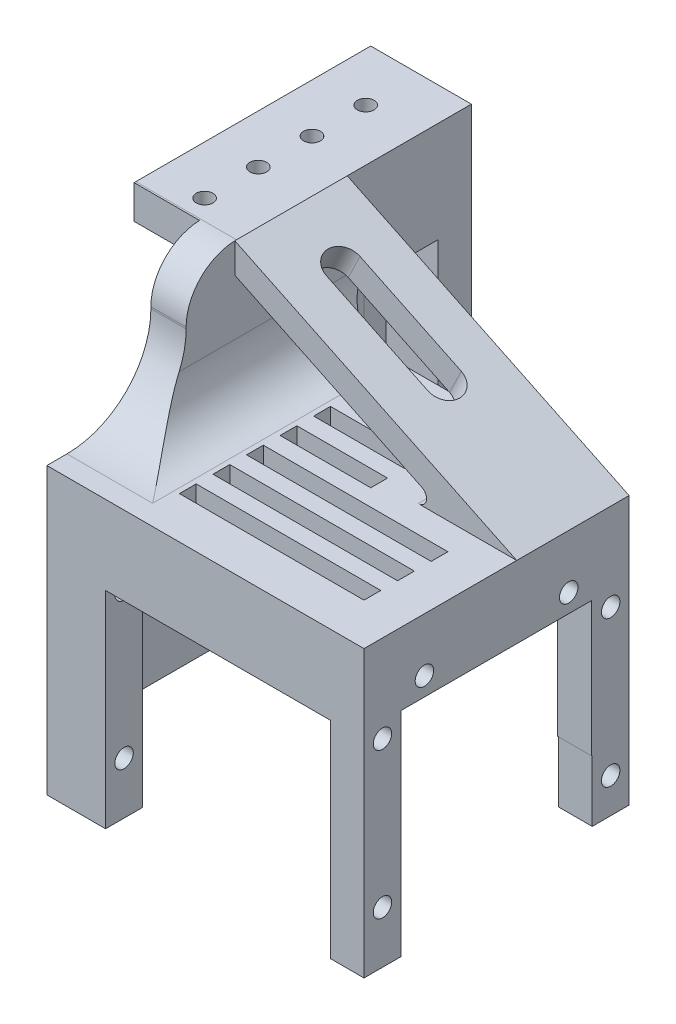
SolidWorks part; units mm, degrees
ref_plane "Front Plane" through (0, 0, 0) normal (0, 0, 1) x (1, 0, 0)
ref_plane "Top Plane" through (0, 0, 0) normal (0, 1, 0) x (1, 0, 0)
ref_plane "Right Plane" through (0, 0, 0) normal (1, 0, 0) x (0, 0, -1)
sketch "Sketch1" plane through (0, 0, 0) normal (0, 0, 1) x (1, 0, 0)
  line L1 (0, 0) -> (57.912, 0)
  line L2 (0, 0) -> (0, 63.754)
  line L3 (0, 63.754) -> (57.912, 63.754)
  line L4 (57.912, 0) -> (57.912, 63.754)
  dimension "D1" = 57.912
  dimension "D2" = 63.754
extrude "Boss-Extrude1" add sketch "Sketch1" against normal blind 58.928
sketch "Sketch3" plane through (0, 0, 0) normal (0, 0, 1) x (1, 0, 0)
  line L0 (42.672, 63.754) -> (0, 43.18)
  line L1 (42.672, 59.2423) -> (14.3644, 45.594)
  line L2 (14.9159, 43.18) -> (42.672, 43.18)
  line L3 (44.437, 60.0933) -> (1.765, 39.5193) construction
  line L4 (0, 63.754) -> (0, 0)
  line L5 (0, 0) -> (57.912, 0)
  line L6 (57.912, 0) -> (57.912, 63.754)
  line L7 (57.912, 63.754) -> (0, 63.754)
  line L8 (0, 63.754) -> (0, 43.18)
  line L9 (5.08, 0) -> (5.08, 31.242)
  line L10 (0, 0) -> (57.912, 0) construction
  line L11 (42.672, 63.754) -> (0, 63.754)
  line L12 (42.672, 59.2423) -> (42.672, 43.18)
  line L13 (5.08, 31.242) -> (39.116, 31.242)
  line L14 (39.116, 31.242) -> (39.116, 0)
  line L15 (5.08, 0) -> (39.116, 0)
  line L16 (48.006, 0) -> (48.006, 11.938)
  line L17 (48.006, 11.938) -> (57.912, 11.938)
  line L18 (57.912, 0) -> (57.912, 63.754) construction
  line L19 (57.912, 11.938) -> (57.912, 0)
  line L20 (48.006, 0) -> (57.912, 0)
  arc A0 (14.3644, 45.594) -> (14.9159, 43.18) centre (14.9159, 44.45) ccw
  dimension "D5" = 1.27
  dimension "D2" = 15.24
  dimension "D3" = 20.574
  dimension "D7" = 5.08
  dimension "D8" = 31.242
  dimension "D9" = 34.036
  dimension "D10" = 9.906
  dimension "D11" = 11.938
  dimension "D1" = 0
  dimension "D4" = 4.064
extrude "Cut-Extrude1" cut sketch "Sketch3" against normal through all
sketch "Sketch4" plane through (0, 63.754, 0) normal (0, 1, 0) x (1, 0, 0)
  line L0 (0, 0) -> (0, 18.796)
  line L1 (0, 58.928) -> (0, 0) construction
  line L2 (0, 18.796) -> (42.672, 18.796)
  line L3 (42.672, 58.928) -> (42.672, 0) construction
  line L4 (42.672, 18.796) -> (42.672, 0)
  line L5 (42.672, 0) -> (0, 0)
  line L6 (57.912, 35.814) -> (48.006, 35.814)
  line L7 (57.912, 58.928) -> (57.912, 0) construction
  line L8 (48.006, 35.814) -> (48.006, 58.928)
  line L9 (48.006, 58.928) -> (57.912, 58.928)
  line L10 (57.912, 58.928) -> (57.912, 35.814)
  line L11 (50.546, 35.814) -> (50.546, 32.512) construction
  circle A0 centre (50.546, 32.512) radius 1.27
  circle A1 centre (50.546, 24.384) radius 1.27
  circle A2 centre (50.546, 16.256) radius 1.27
  circle A3 centre (50.546, 8.128) radius 1.27
  dimension "D5" = 2.54
  dimension "D1" = 18.796
  dimension "D2" = 9.906
  dimension "D3" = 7.366
  dimension "D4" = 3.302
  dimension "D8" = 35.814
  dimension "D6" = 4
extrude "Cut-Extrude2" cut sketch "Sketch4" against normal through all
fillet "Fillet1" radius 2.54 1 edges at (42.672, 21.59, -18.796)
sketch "Sketch6" plane through (0, 63.754, 0) normal (0, 1, 0) x (1, 0, 0)
  line L0 (42.672, 35.814) -> (0, 35.814)
  line L1 (0, 58.928) -> (0, 18.796) construction
  line L2 (0, 35.814) -> (0, 58.928)
  line L3 (0, 58.928) -> (48.006, 58.928)
  line L4 (48.006, 58.928) -> (48.006, 43.18)
  line L5 (48.006, 58.928) -> (48.006, 35.814) construction
  line L6 (48.006, 43.18) -> (42.672, 43.18)
  line L7 (42.672, 58.928) -> (42.672, 18.796) construction
  line L8 (42.672, 43.18) -> (42.672, 35.814)
  line L9 (48.006, 35.814) -> (57.912, 35.814) construction
  dimension "D1" = 15.748
extrude "Cut-Extrude3" cut sketch "Sketch6" against normal blind 20.574
fillet "Fillet2" radius 12.7 1 edges at (45.339, 43.18, -43.18)
fillet "Fillet3" radius 7.62 1 edges at (42.672, 43.18, -36.068)
fillet "Fillet4" radius 7.62 1 edges at (45.339, 63.754, -43.18)
sketch "Sketch7" plane through (-16.8922, 35.0356, 0) normal (-0.4343, 0.9008, 0) x (0.9008, 0.4343, 0)
  line L0 (57.4899, 18.796) -> (57.4899, 24.638) construction
  line L1 (18.753, 18.796) -> (66.1259, 18.796) construction
  line L2 (57.4899, 24.638) -> (66.1259, 24.638) construction
  line L4 (57.4899, 24.638) -> (40.4719, 24.638)
  line L5 (57.4899, 29.718) -> (40.4719, 29.718)
  line L6 (66.1259, 35.56) -> (66.1259, 18.796) construction
  arc A0 (40.4719, 29.718) -> (40.4719, 24.638) centre (40.4719, 27.178) ccw
  arc A1 (57.4899, 29.718) -> (57.4899, 24.638) centre (57.4899, 27.178) cw
  dimension "D1" = 8.636
  dimension "D2" = 5.842
  dimension "D4" = 17.018
  dimension "D3" = 5.08
extrude "Cut-Extrude4" cut sketch "Sketch7" along direction (-0.4343, 0.9008, 0) on the side against the normal up to next (4.064 mm away)
sketch "Sketch8" plane through (0, 43.18, 0) normal (0, 1, 0) x (1, 0, 0)
  line L0 (6.35, 52.578) -> (34.29, 52.578)
  line L1 (34.29, 52.578) -> (34.29, 50.038)
  line L2 (34.29, 50.038) -> (6.35, 50.038)
  line L3 (6.35, 50.038) -> (6.35, 52.578)
  line L4 (0, 58.928) -> (0, 35.814) construction
  line L5 (0, 58.928) -> (48.006, 58.928) construction
  line L6 (34.29, 44.958) -> (6.35, 44.958)
  line L7 (34.29, 47.498) -> (34.29, 44.958)
  line L8 (6.35, 47.498) -> (34.29, 47.498)
  line L9 (6.35, 44.958) -> (6.35, 47.498)
  line L10 (34.29, 39.878) -> (6.35, 39.878)
  line L11 (34.29, 42.418) -> (34.29, 39.878)
  line L12 (6.35, 42.418) -> (34.29, 42.418)
  line L13 (6.35, 39.878) -> (6.35, 42.418)
  line L14 (34.29, 37.338) -> (20.574, 37.338)
  line L15 (34.29, 37.338) -> (34.29, 34.798)
  line L16 (34.29, 34.798) -> (20.574, 34.798)
  line L17 (20.574, 34.798) -> (20.574, 37.338)
  line L18 (34.29, 37.338) -> (6.35, 37.338) construction
  line L19 (34.29, 29.718) -> (20.574, 29.718)
  line L20 (34.29, 32.258) -> (34.29, 29.718)
  line L21 (34.29, 32.258) -> (20.574, 32.258)
  line L22 (20.574, 29.718) -> (20.574, 32.258)
  line L23 (34.29, 24.638) -> (20.574, 24.638)
  line L24 (34.29, 27.178) -> (34.29, 24.638)
  line L25 (34.29, 27.178) -> (20.574, 27.178)
  line L26 (20.574, 24.638) -> (20.574, 27.178)
  dimension "D1" = 6.35
  dimension "D2" = 6.35
  dimension "D3" = 2.54
  dimension "D4" = 27.94
  dimension "D7" = 2.54
  dimension "D8" = 13.716
  dimension "D6" = 2.54
  dimension "D5" = 3
  dimension "D9" = 3
extrude "Cut-Extrude5" cut sketch "Sketch8" against normal through all
sketch "Sketch9" plane through (0, 31.242, 0) normal (0, -1, 0) x (1, 0, 0)
  line L4 (39.116, -19.304) -> (5.08, -19.304)
  line L5 (5.08, -58.42) -> (39.116, -58.42)
  line L8 (39.116, -58.928) -> (39.116, -18.796)
  line L9 (39.116, -18.796) -> (5.08, -18.796)
  line L10 (5.08, -18.796) -> (5.08, -58.928)
  line L11 (5.08, -58.928) -> (39.116, -58.928)
  line L12 (39.116, -58.42) -> (39.116, -19.304)
  line L14 (5.08, -19.304) -> (5.08, -58.42)
  dimension "D1" = 0
extrude "Cut-Extrude6" cut sketch "Sketch9" against normal blind 5.588
sketch "Sketch10" plane through (5.08, 0, 0) normal (1, 0, 0) x (0, 0, -1)
  line L0 (58.42, 31.242) -> (54.6195, 36.83)
  line L1 (58.42, 36.83) -> (19.304, 36.83) construction
  line L2 (58.928, 31.242) -> (58.42, 31.242) construction
  line L3 (54.6195, 36.83) -> (58.42, 36.83)
  line L4 (58.42, 36.83) -> (58.42, 31.242)
  dimension "D1" = 124.22
extrude "Boss-Extrude3" add sketch "Sketch10" along direction (1, 0, 0) on the side of the normal up to next (34.036 mm away)
sketch "Sketch11" plane through (0, 31.242, 0) normal (0, -1, 0) x (1, 0, 0)
  line L0 (22.098, -58.928) -> (22.098, -18.796) construction
  line L1 (39.116, -58.928) -> (5.08, -58.928) construction
  line L2 (39.116, -18.796) -> (5.08, -18.796) construction
  line L3 (22.098, -38.862) -> (6.9192, -38.862) construction
ref_plane "Plane1" through (0, 0, -38.862) normal (0, 0, 1) x (1, 0, 0)
mirror "Mirror1" about plane through (0, 0, -38.862) normal (0, 0, 1) of "Boss-Extrude3"
fillet "Fillet5" radius 3.048 2 edges at (22.098, 36.83, -54.6195) (22.098, 36.83, -23.1045)
sketch "Sketch12" plane through (42.672, 0, 0) normal (-1, 0, 0) x (0, 0, 1)
  line L0 (0, 0) -> (0, 63.754) construction
  line L1 (-5.08, 27.94) -> (-12.954, 27.94)
  line L2 (-5.08, 27.94) -> (-5.08, 48.514)
  line L3 (-5.08, 48.514) -> (-12.954, 48.514)
  line L4 (-12.954, 27.94) -> (-12.954, 48.514)
  line L5 (0, 63.754) -> (-18.796, 63.754) construction
  line L6 (-53.34, 0) -> (-53.34, 11.938)
  line L7 (-58.928, 0) -> (-18.796, 0) construction
  line L8 (-53.34, 11.938) -> (-24.384, 11.938)
  line L9 (-24.384, 11.938) -> (-24.384, 2.5976)
  line L10 (-24.384, 2.5976) -> (-18.796, 2.5976)
  line L11 (-18.796, 0) -> (-18.796, 43.18) construction
  line L12 (-18.796, 2.5976) -> (-18.796, 11.938)
  line L13 (-18.796, 11.938) -> (0, 11.938)
  line L14 (0, 11.938) -> (0, 0)
  line L15 (0, 0) -> (-53.34, 0)
  line L16 (-58.928, 43.18) -> (-58.928, 0) construction
  dimension "D1" = 5.08
  dimension "D2" = 7.874
  dimension "D3" = 20.574
  dimension "D4" = 15.24
  dimension "D5" = 5.588
  dimension "D6" = 5.588
  dimension "D7" = 11.938
extrude "Cut-Extrude7" cut sketch "Sketch12" against normal through all both and the other way through all
sketch "Sketch14" plane through (0, 0, 0) normal (-1, 0, 0) x (0, 0, 1)
  line L0 (-53.34, 11.938) -> (-53.34, 32.258)
  line L1 (-53.34, 11.938) -> (-24.5287, 11.938)
  line L2 (-24.384, 11.938) -> (-53.34, 11.938) construction
  line L3 (-24.5287, 11.938) -> (-24.5287, 32.258)
  line L4 (-24.5287, 32.258) -> (-53.34, 32.258)
  dimension "D1" = 20.32
extrude "Cut-Extrude8" cut sketch "Sketch14" against normal up to surface (42.672 mm away) up to face at (42.672, 38.227, -9.017)
sketch "Sketch17" plane through (0, 0, 0) normal (-1, 0, 0) x (0, 0, 1)
  line L0 (-58.928, 0) -> (-53.34, 0) construction
  line L1 (-56.134, 0) -> (-56.134, 7.874) construction
  line L2 (-21.59, 2.5976) -> (-21.59, 0) construction
  line L3 (-18.796, 2.5976) -> (-24.384, 2.5976) construction
  line L4 (-38.862, 0) -> (-38.862, 39.1109) construction
  line L5 (-56.134, 0) -> (-21.59, 0) construction
  line L6 (-49.784, 32.258) -> (-49.784, 35.052) construction
  line L7 (-24.5287, 32.258) -> (-53.34, 32.258) construction
  circle A0 centre (-56.134, 7.874) radius 1.397
  circle A1 centre (-56.134, 29.972) radius 1.397
  circle A2 centre (-49.784, 35.052) radius 1.397
  circle A3 centre (-21.59, 7.874) radius 1.397
  circle A4 centre (-21.59, 29.972) radius 1.397
  circle A5 centre (-27.94, 35.052) radius 1.397
  dimension "D2" = 2.794
  dimension "D6" = 2.794
  dimension "D1" = 7.874
  dimension "D3" = 2
  dimension "D4" = 2.794
  dimension "D5" = 3.556
extrude "Cut-Extrude9" cut sketch "Sketch17" against normal through all
sketch "Sketch18" plane through (0, 0, -35.814) normal (0, 0, -1) x (-1, 0, 0)
  line L0 (-57.912, 58.6698) -> (-48.006, 58.6698)
  line L1 (-57.912, 11.938) -> (-57.912, 63.7498) construction
  line L2 (-48.006, 58.6698) -> (-48.006, 53.8438)
  line L3 (-48.006, 53.8438) -> (-53.086, 53.8438)
  line L4 (-53.086, 53.8438) -> (-53.086, 50.5418)
  line L5 (-53.086, 50.5418) -> (-48.006, 50.5418)
  line L6 (-48.006, 50.5418) -> (-48.006, 25.146)
  line L7 (-48.006, 37.8439) -> (-57.912, 37.8439) construction
  line L8 (-57.912, 17.018) -> (-57.912, 58.6698)
  line L9 (-57.912, 63.7519) -> (-57.912, 11.938) construction
  line L10 (-57.912, 63.754) -> (-57.912, 63.7498) construction
  line L11 (-48.006, 63.7498) -> (-57.912, 63.7498) construction
  line L12 (-57.912, 11.9359) -> (-57.912, 63.7498) construction
  line L13 (-53.086, 25.146) -> (-48.006, 25.146)
  line L14 (-53.086, 21.844) -> (-53.086, 25.146)
  line L15 (-48.006, 21.844) -> (-53.086, 21.844)
  line L16 (-48.006, 17.018) -> (-48.006, 21.844)
  line L17 (-57.912, 17.018) -> (-48.006, 17.018)
  point P15 (-57.912, 37.8449)
  dimension "D1" = 5.08
  dimension "D2" = 9.906
  dimension "D3" = 4.826
  dimension "D4" = 5.08
  dimension "D5" = 3.302
extrude "Cut-Extrude10" cut sketch "Sketch18" against normal blind 30.734
sketch "Sketch19" plane through (0, 25.146, 0) normal (0, 1, 0) x (1, 0, 0)
  circle A0 centre (50.546, 8.128) radius 1.27 construction
  circle A1 centre (50.546, 16.256) radius 1.27 construction
  circle A2 centre (50.546, 24.384) radius 1.27 construction
  circle A3 centre (50.546, 32.512) radius 1.27 construction
  circle A4 centre (50.546, 8.128) radius 1.27 construction
  circle A5 centre (50.546, 16.256) radius 1.27 construction
  circle A6 centre (50.546, 24.384) radius 1.27 construction
  circle A7 centre (50.546, 32.512) radius 1.27 construction
  circle A8 centre (50.546, 32.512) radius 2.5908
  circle A9 centre (50.546, 24.384) radius 2.5908
  circle A10 centre (50.546, 16.256) radius 2.5908
  circle A11 centre (50.546, 8.128) radius 2.5908
  dimension "D1" = 1.3208
  dimension "D2" = 1.3208
  dimension "D3" = 1.3208
  dimension "D4" = 1.3208
extrude "Cut-Extrude13" cut sketch "Sketch19" against normal blind 1.5875
sketch "Sketch20" plane through (0, 50.5418, 0) normal (0, -1, 0) x (1, 0, 0)
  circle A0 centre (50.546, -8.128) radius 1.27 construction
  circle A1 centre (50.546, -16.256) radius 1.27 construction
  circle A2 centre (50.546, -24.384) radius 1.27 construction
  circle A3 centre (50.546, -32.512) radius 1.27 construction
  circle A4 centre (50.546, -8.128) radius 1.27 construction
  circle A5 centre (50.546, -16.256) radius 1.27 construction
  circle A6 centre (50.546, -24.384) radius 1.27 construction
  circle A7 centre (50.546, -32.512) radius 1.27 construction
  circle A8 centre (50.546, -8.128) radius 2.5908
  circle A9 centre (50.546, -16.256) radius 2.5908
  circle A10 centre (50.546, -24.384) radius 2.5908
  circle A11 centre (50.546, -32.512) radius 2.5908
  dimension "D1" = 1.3208
  dimension "D2" = 1.3208
  dimension "D3" = 1.3208
  dimension "D4" = 1.3208
extrude "Cut-Extrude14" cut sketch "Sketch20" against normal blind 1.5875
mirror "Mirror2" about plane through (0, 0, 0) normal (0, 0, 1) of bodies 116
sketch "Sketch21" plane through (0, 63.754, 0) normal (0, 1, 0) x (1, 0, 0)
  line L0 (83.5536, 0) -> (-36.9665, 0)
  line L2 (-36.9665, 0) -> (-36.9665, 73.6411)
  line L3 (-36.9665, 73.6411) -> (83.5536, 73.6411)
  line L4 (83.5536, 73.6411) -> (83.5536, 0)
extrude "Cut-Extrude15" cut sketch "Sketch21" against normal through all
mirror "Mirror3" about plane through (57.912, 0, -58.928) normal (1, 0, 0) of bodies 118
sketch "Sketch22" plane through (0, 63.754, 0) normal (0, 1, 0) x (1, 0, 0)
  line L0 (57.912, 23.0082) -> (57.912, -82.454)
  line L2 (57.912, -82.454) -> (-28.6858, -82.454)
  line L3 (-28.6858, -82.454) -> (-28.6858, 23.0082)
  line L4 (-28.6858, 23.0082) -> (57.912, 23.0082)
extrude "Cut-Extrude16" cut sketch "Sketch22" against normal through all
